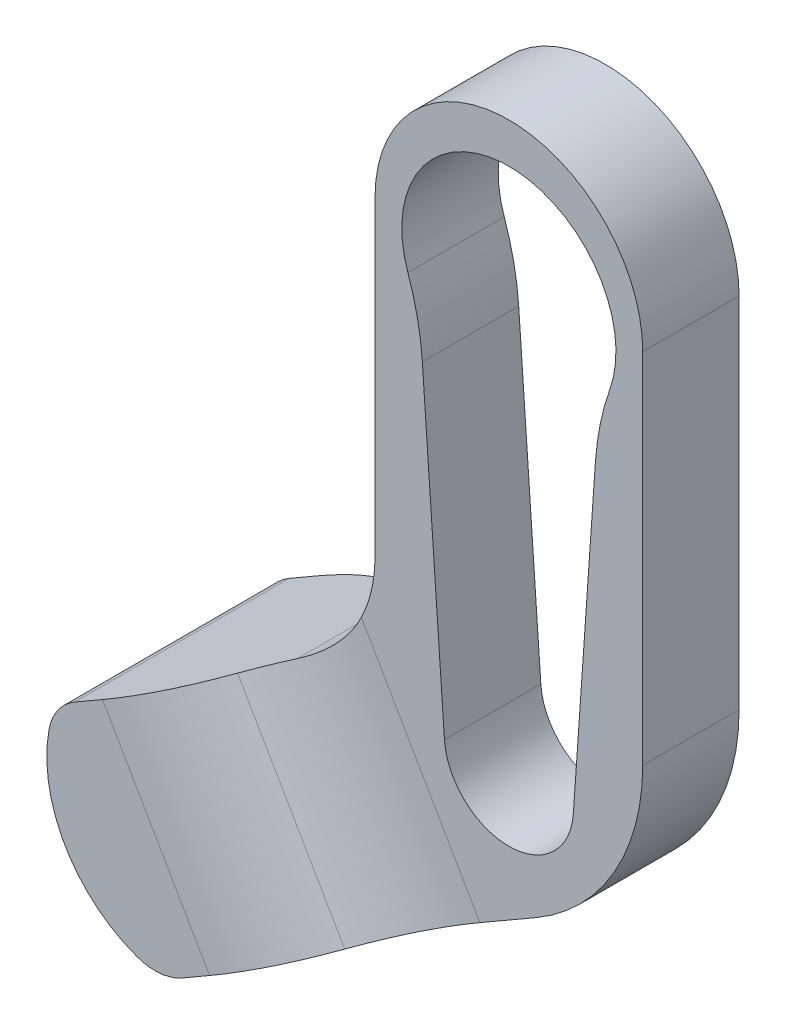
SolidWorks part; units mm, degrees
ref_plane "前视基准面" through (0, 0, 0) normal (0, 0, 1) x (1, 0, 0)
ref_plane "上视基准面" through (0, 0, 0) normal (0, 1, 0) x (1, 0, 0)
ref_plane "右视基准面" through (0, 0, 0) normal (1, 0, 0) x (0, 0, -1)
sketch "草图2" plane through (0, 0, 0) normal (0, 0, 1) x (1, 0, 0)
  line L0 (-36.1595, 31.672) -> (-36.1595, 46.2079)
  line L2 (-26.1595, 46.2079) -> (-26.1595, 28.2079)
  line L3 (-26.1595, 28.2079) -> (-41.1702, 19.5415)
  line L5 (-45.1702, 26.4697) -> (-36.1595, 31.672)
  line L6 (-36.1595, 31.672) -> (-26.1595, 28.2079) construction
  line L7 (-34.651, 45.4638) -> (-33.5663, 29.9523)
  line L8 (-27.2543, 51.3808) -> (-28.7527, 29.9523)
  line L9 (-31.1595, 49.7079) -> (-31.1595, 25.5666) construction
  line L10 (-41.1299, 24.1836) -> (-29.5641, 30.8611) construction
  line L13 (-26.1595, 46.2079) -> (-41.1702, 19.5415) construction
  arc A1 (-36.1595, 46.2079) -> (-26.1595, 46.2079) centre (-31.1595, 46.2079) cw
  circle A2 centre (-31.1595, 45.7079) radius 4
  circle A3 centre (-31.1595, 30.1206) radius 2.4127
  circle A4 centre (-31.1595, 45.7079) radius 3.5
  arc A5 (-41.1702, 19.5415) -> (-42.8434, 19.3903) centre (-42.1702, 21.2736) cw
  arc A6 (-45.1702, 26.4697) -> (-46.1377, 25.0963) centre (-44.1702, 24.7377) ccw
  arc A7 (-46.1377, 25.0963) -> (-42.8434, 19.3903) centre (-41.1299, 24.1836) ccw
  point P8 (-31.1595, 45.7079)
  point P11 (-31.1595, 30.1206)
  point P18 (-31.1595, 27.7079)
  point P19 (-31.1595, 49.7079)
  point P28 (-41.748, 19.2079)
  point P31 (-45.748, 26.1361)
  dimension "D8" = 8
  dimension "D9" = 8
  dimension "D6" = 7
  dimension "D11" = 2
  dimension "D12" = 4
  dimension "D1" = 120
  dimension "D2" = 10
  dimension "D3" = 8
  dimension "D4" = 18
  dimension "D5" = 18
  dimension "D7" = 0.5
  dimension "D10" = 22
extrude "凸台-拉伸1" add sketch "草图2" along normal mid plane 8 contours A1 L0 L5 L3 L2 A3 L7 A2 L8 region at (-35.2561, 31.2719, 0)
fillet "圆角1" radius 8 1 edges at (-26.1595, 28.2079, 0)
fillet "圆角2" radius 5 1 edges at (-36.1595, 31.672, 0)
fillet "圆角3" radius 10 2 edges at (-34.5159, 43.532, 0) (-27.8031, 43.532, 0)
ref_plane "基准面1" through (-15.9673, -9.2187, 0) normal (0.866, 0.5, 0) x (0, 0, -1)
sketch "草图5" plane through (-15.9673, -9.2187, 0) normal (0.866, 0.5, 0) x (0, 0, -1)
  line L0 (0, 50.3428) -> (0, 24.6545) construction
  line L1 (-4, 53.3655) -> (-4, 42.7226) construction
  line L2 (-1.8, 66.9785) -> (1.8, 66.9785)
  line L3 (-1.8, 66.9785) -> (-1.8, 36.9785)
  line L4 (-1.8, 36.9785) -> (1.8, 36.9785)
  line L5 (1.8, 66.9785) -> (1.8, 36.9785)
  line L6 (4, 52.1288) -> (4, 59.164) construction
  dimension "D1" = 3.6
  dimension "D2" = 30
extrude "切除-拉伸1" cut sketch "草图5" along normal through all flip side to cut contours L3 L2 L5 L4
fillet "圆角4" radius 10 2 edges at (-36.7215, 26.7287, 4) (-36.7215, 26.7287, -4)
fillet "圆角5" radius 10 2 edges at (-36.7215, 26.7287, -1.8) (-36.7215, 26.7287, 1.8)
